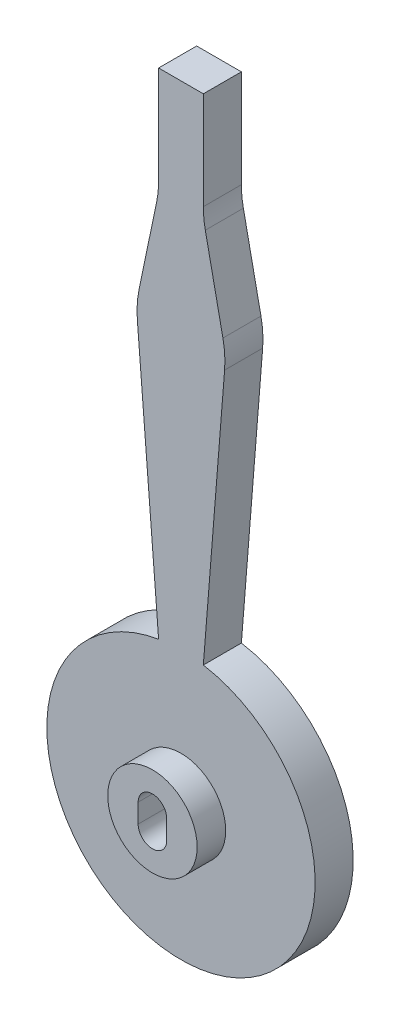
SolidWorks part; units mm, degrees
ref_plane "Front Plane" through (0, 0, 0) normal (0, 0, 1) x (1, 0, 0)
ref_plane "Top Plane" through (0, 0, 0) normal (0, 1, 0) x (1, 0, 0)
ref_plane "Right Plane" through (0, 0, 0) normal (1, 0, 0) x (0, 0, -1)
sketch "Sketch1" plane through (0, 0, 0) normal (0, 0, 1) x (1, 0, 0)
  line L0 (0, 0) -> (4.7, 0)
  line L1 (0, -14.1) -> (0, 65.9)
  line L2 (-4.7, 13.2936) -> (-4.7, 43.2936)
  line L3 (4.7, 13.2936) -> (4.7, 43.2936)
  line L4 (-4.4082, 44.6972) -> (-2.5594, 53.5898)
  line L5 (-2.35, 55.6253) -> (-2.35, 65.9)
  line L6 (-2.35, 65.9) -> (2.35, 65.9)
  line L7 (2.35, 65.9) -> (2.35, 55.6253)
  line L8 (2.5594, 53.5898) -> (4.4082, 44.6972)
  line L9 (-2.35, 13.9028) -> (-4.5857, 41.8646)
  line L10 (2.35, 13.9028) -> (4.5857, 41.8646)
  circle A0 centre (0, 0) radius 4.7
  circle A1 centre (0, 0) radius 14.1
  arc A2 (4.4082, 44.6972) -> (4.5857, 41.8646) centre (-5.3824, 42.6616) cw
  arc A3 (-4.4082, 44.6972) -> (-4.5857, 41.8646) centre (5.3824, 42.6616) ccw
  arc A4 (-2.35, 55.6253) -> (-2.5594, 53.5898) centre (-12.35, 55.6253) cw
  arc A5 (2.35, 55.6253) -> (2.5594, 53.5898) centre (12.35, 55.6253) ccw
  point P7 (-4.7, 0)
  point P8 (14.1, 0)
  point P9 (-14.1, 0)
  point P10 (4.7, 13.2936)
  point P11 (-4.7, 13.2936)
  point P16 (2.35, 54.5968)
  point P17 (-2.35, 54.5968)
  point P22 (-2.35, 13.9028)
  point P23 (2.35, 13.9028)
  point P34 (-2.35, 54.5968)
  point P37 (2.35, 54.5968)
  dimension "D3" = 28.2
  dimension "D8" = 10
  dimension "D9" = 10
  dimension "D10" = 10
  dimension "D11" = 10
  dimension "D1" = 4.7
  dimension "D2" = 80
  dimension "D4" = 30
  dimension "D5" = 30
  dimension "D6" = 13.2936
  dimension "D7" = 13.2936
  dimension "D12" = 4.7
  dimension "D13" = 27.9618
  dimension "D14" = 27.9618
  dimension "D15" = 10.2747
  dimension "D16" = 10.2747
  dimension "D17" = 23.49
extrude "Boss-Extrude1" add sketch "Sketch1" along normal blind 4 contours A1 L1 A0 | L1 A1 A0 | L5 A4 L4 A3 L9 A1 L1 L6 | A5 L7 L6 L1 A1 L10 A2 L8 region at (6.4829, 0, 0) region at (-6.4829, 0, 0) region at (-1.7258, 39.2066, 0) region at (1.7258, 39.2066, 0)
extrude "Boss-Extrude2" add sketch "Sketch1<3>" along normal blind 7 contours L1 A0 L0 | L0 A0 L1 | L1 A0 region at (1.9947, 1.9947, 0) region at (1.9947, -1.9947, 0) region at (-1.9947, 0, 0)
sketch "Sketch1<3>" plane through (0, 0, 0) normal (0, 0, 1) x (1, 0, 0) same geometry as "Sketch1"
sketch "Sketch2" plane through (0, 0, 7) normal (0, 0, 1) x (1, 0, 0)
  line L0 (0, 1) -> (0, -1) construction
  line L1 (1.5, 1) -> (1.5, -1)
  line L2 (-1.5, 1) -> (-1.5, -1)
  arc A0 (1.5, 1) -> (-1.5, 1) centre (0, 1) ccw
  arc A1 (-1.5, -1) -> (1.5, -1) centre (0, -1) ccw
  point P3 (0, 0)
  point P8 (0, 2.5)
  point P9 (0, -2.5)
  point P10 (0, 0)
  dimension "D1" = 5
  dimension "D2" = 3
extrude "Cut-Extrude1" cut sketch "Sketch2" against normal blind 3
